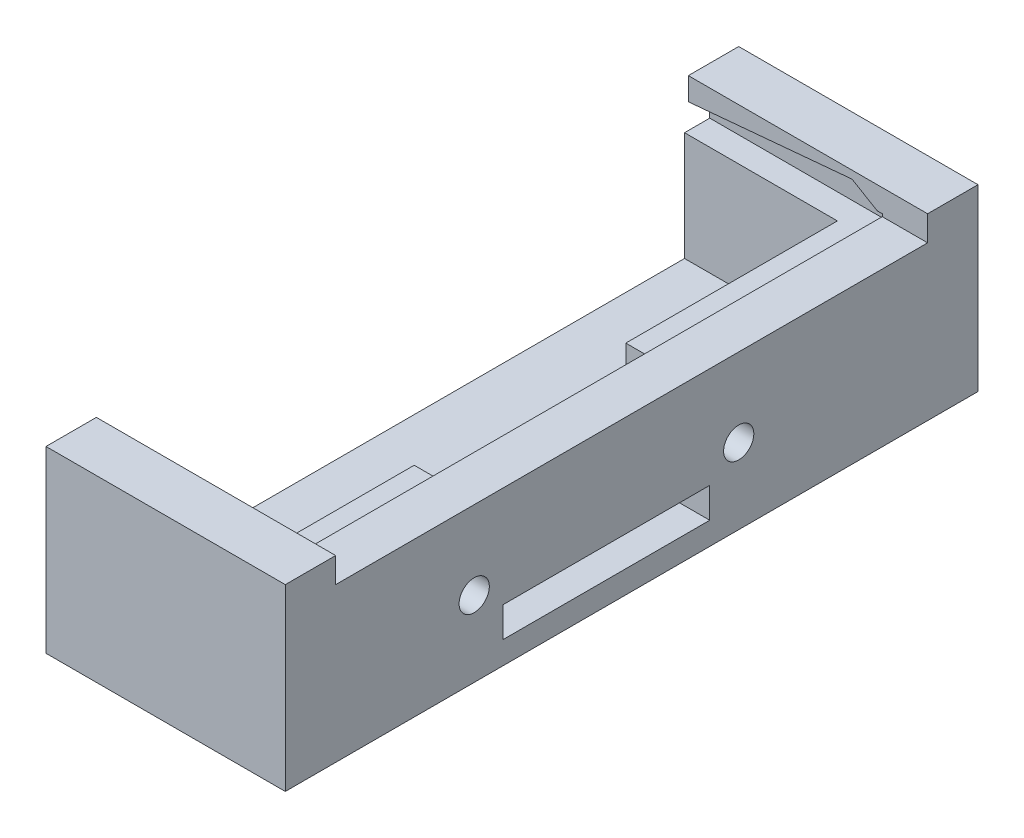
SolidWorks part; units mm, degrees
note: The reader was unsure of these and kept them because the rebuilt part matched: shared geometry of "Sketch8<2>".
ref_plane "Front Plane" through (0, 0, 0) normal (0, 0, 1) x (1, 0, 0)
ref_plane "Top Plane" through (0, 0, 0) normal (0, 1, 0) x (1, 0, 0)
ref_plane "Right Plane" through (0, 0, 0) normal (1, 0, 0) x (0, 0, -1)
sketch "Sketch1" plane through (0, 0, 0) normal (1, 0, 0) x (0, 0, -1)
  line L0 (39.37, -10.9855) -> (19.05, -10.9855) construction
  line L1 (-3.175, -13.5255) -> (66.675, -13.5255)
  line L2 (-3.175, -13.5255) -> (-3.175, 4.54)
  line L3 (-3.175, 4.54) -> (66.675, 4.54)
  line L4 (66.675, -13.5255) -> (66.675, 4.54)
  line L5 (0, 2) -> (0, 0) construction
  line L6 (63.5, 2) -> (63.5, 0) construction
  line L7 (0, 2) -> (63.5, 2) construction
  point P9 (0, 1)
  dimension "D1" = 2.54
  dimension "D2" = 3.175
  dimension "D3" = 3.175
  dimension "D4" = 2.54
extrude "Boss-Extrude1" add sketch "Sketch1" against normal blind 19.05 and the other way blind 5.08
sketch "Sketch2" plane through (0, 2, 0) normal (0, 1, 0) x (1, 0, 0)
  line L0 (0, 63.5) -> (-96.52, 63.5) construction
  line L1 (0.508, -0.254) -> (-97.028, -0.254)
  line L2 (0.508, -0.254) -> (0.508, 63.754)
  line L3 (0.508, 63.754) -> (-97.028, 63.754)
  line L4 (-97.028, -0.254) -> (-97.028, 63.754)
  line L5 (-96.52, 0) -> (0, 0) construction
  line L6 (-96.52, 63.5) -> (-96.52, 0) construction
  line L7 (0, 0) -> (0, 63.5) construction
  dimension "D1" = 0.254
  dimension "D2" = 0.254
  dimension "D3" = 0.508
  dimension "D4" = 0.508
extrude "Cut-Extrude1" cut sketch "Sketch2" against normal offset from surface 0.254 and the other way blind 0.254
sketch "Sketch3" plane through (5.08, 0, 0) normal (1, 0, 0) x (0, 0, -1)
  line L0 (39.37, -8.4455) -> (19.05, -8.4455) construction
  line L1 (18.796, -8.1915) -> (39.624, -8.1915)
  line L2 (18.796, -8.1915) -> (18.796, -11.2395)
  line L3 (18.796, -11.2395) -> (39.624, -11.2395)
  line L4 (39.624, -8.1915) -> (39.624, -11.2395)
  line L5 (39.37, -10.9855) -> (19.05, -10.9855) construction
  line L6 (19.05, -10.9855) -> (19.05, -8.4455) construction
  line L7 (39.37, -10.9855) -> (39.37, -8.4455) construction
  dimension "D1" = 0.254
  dimension "D2" = 0.254
  dimension "D3" = 0.254
  dimension "D4" = 0.254
extrude "Cut-Extrude2" cut sketch "Sketch3" against normal through all both and the other way through all
sketch "Sketch4" plane through (0, 4.54, 0) normal (0, 1, 0) x (1, 0, 0)
  line L0 (5.08, 66.675) -> (5.08, -3.175) construction
  line L1 (5.08, 61.595) -> (-19.05, 61.595)
  line L2 (5.08, 61.595) -> (5.08, 1.905)
  line L3 (5.08, 1.905) -> (-19.05, 1.905)
  line L4 (-19.05, 61.595) -> (-19.05, 1.905)
  line L5 (-19.05, 66.675) -> (-19.05, -3.175) construction
  line L6 (5.08, 66.675) -> (-19.05, 66.675) construction
  line L7 (5.08, -3.175) -> (-19.05, -3.175) construction
  dimension "D1" = 5.08
  dimension "D2" = 5.08
extrude "Cut-Extrude3" cut sketch "Sketch4" against normal up to surface (2.54 mm away)
sketch "Sketch5" plane through (0, -0.254, 0) normal (0, 1, 0) x (1, 0, 0)
  line L0 (-19.05, -0.254) -> (-19.05, 63.754) construction
  line L1 (-0.5904, 39.878) -> (-19.05, 39.878)
  line L2 (-0.5904, 39.878) -> (-0.5904, 18.542)
  line L3 (-0.5904, 18.542) -> (-19.05, 18.542)
  line L4 (-19.05, 39.878) -> (-19.05, 18.542)
  line L5 (-0.635, 39.37) -> (-3.175, 39.37) construction
  line L6 (-3.175, 19.05) -> (-0.635, 19.05) construction
  dimension "D1" = 0.508
  dimension "D2" = 0.508
extrude "Cut-Extrude4" cut sketch "Sketch5" against normal up to surface (10.9855 mm away) up to face at (-6.985, -11.2395, -29.21)
sketch "Sketch6" plane through (-19.05, 0, 0) normal (-1, 0, 0) x (0, 0, 1)
  line L0 (-39.878, -0.254) -> (-63.754, -0.254) construction
  line L1 (-61.214, -0.254) -> (-2.286, -0.254)
  line L2 (-61.214, -0.254) -> (-61.214, -11.2395)
  line L3 (-61.214, -11.2395) -> (-2.286, -11.2395)
  line L4 (-2.286, -0.254) -> (-2.286, -11.2395)
  line L5 (-18.542, -11.2395) -> (-39.878, -11.2395) construction
  line L6 (-63.754, -0.254) -> (-63.754, 2.254) construction
  line L7 (0.254, 2.254) -> (0.254, -0.254) construction
  point P10 (-63.754, 1)
  dimension "D1" = 2.54
  dimension "D2" = 2.54
extrude "Cut-Extrude5" cut sketch "Sketch6" against normal offset from surface (15.4116 mm away) 3.048 up to face at (-0.5904, -7.7311, -29.21)
sketch "Sketch7" plane through (5.08, 0, 0) normal (1, 0, 0) x (0, 0, -1)
  line L1 (-3.175, -13.5255) -> (66.675, -13.5255) construction
  line L2 (15.875, -5.9055) -> (19.05, -5.9055) construction
  line L3 (39.37, -10.9855) -> (39.37, -8.4455) construction
  line L4 (19.05, -10.9855) -> (19.05, -8.4455) construction
  line L5 (42.545, -5.9055) -> (39.37, -5.9055) construction
  circle A0 centre (15.875, -5.9055) radius 1.524
  circle A1 centre (42.545, -5.9055) radius 1.524
  point P11 (19.05, -9.7155)
  point P14 (39.37, -9.7155)
  dimension "D1" = 3.048
  dimension "D2" = 7.62
  dimension "D3" = 3.175
extrude "Cut-Extrude6" cut sketch "Sketch7" against normal through all
sketch "Sketch8" plane through (0, 0, -61.595) normal (0, 0, 1) x (1, 0, 0)
  line L0 (-19.05, 2.254) -> (-2.54, 3.754)
  line L1 (-2.54, 3.754) -> (0, 2.254)
  line L2 (0.508, 2.254) -> (-19.05, 2.254) construction
  line L3 (0, 2.254) -> (-19.05, 2.254)
  line L5 (-2.54, 2.254) -> (-2.54, 3.754) construction
  point P3 (0, 2.254)
  dimension "D1" = 2.54
  dimension "D2" = 1.5
  dimension "D3" = 0.508
extrude "Cut-Extrude7" cut sketch "Sketch8" against normal up to vertex (2.159 mm away) up to point (-19.05, 2.254, -63.754)
extrude "Cut-Extrude9" cut sketch "Sketch8<2>" along normal up to surface (2.159 mm away) from surface at 59.69 up to face at (-9.271, 1, 0.254) starting at face at (-4.4873, 2.9313, -1.905)
sketch "Sketch8<2>" plane through (0, 0, -61.595) normal (0, 0, 1) x (1, 0, 0) same geometry as "Sketch8"
